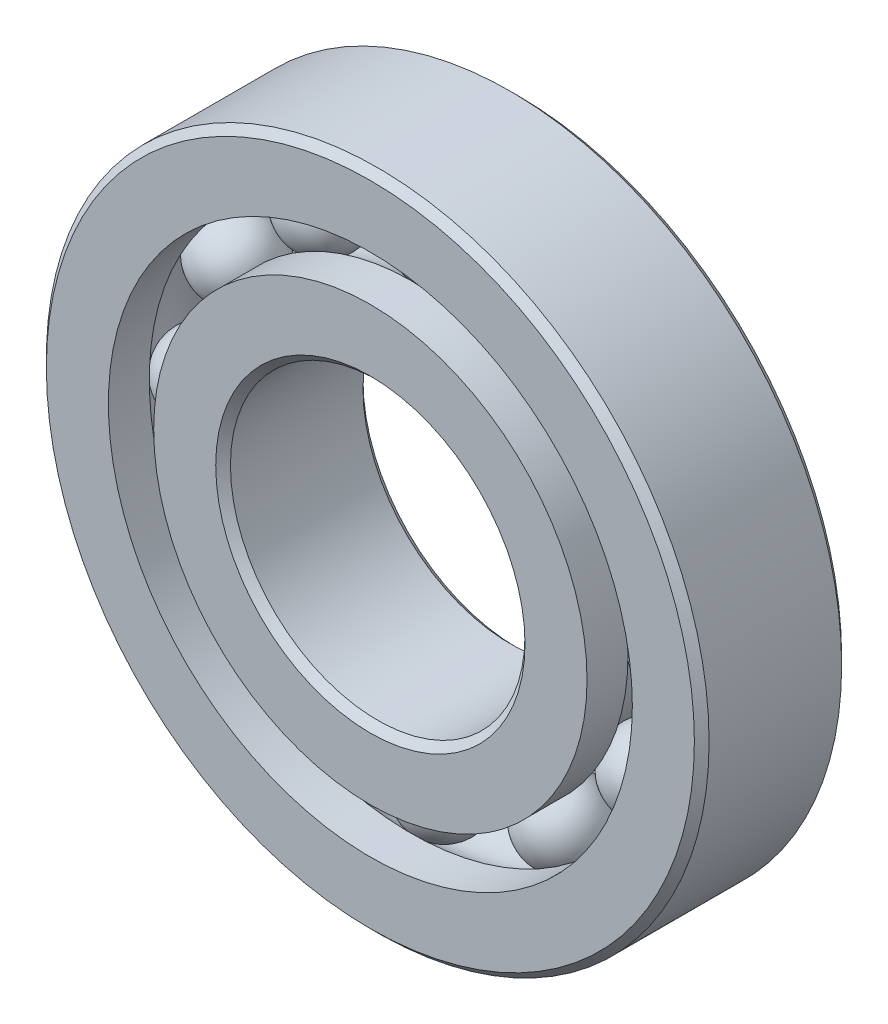
SolidWorks part; units mm, degrees
ref_plane "Front Plane" through (0, 0, 0) normal (0, 0, 1) x (1, 0, 0)
ref_plane "Top Plane" through (0, 0, 0) normal (0, 1, 0) x (1, 0, 0)
ref_plane "Right Plane" through (0, 0, 0) normal (1, 0, 0) x (0, 0, -1)
sketch "Sketch1" plane through (0, 0, 0) normal (1, 0, 0) x (0, 0, -1)
  line L0 (-3.175, 0) -> (3.175, 0) construction
  line L1 (0, 14.2875) -> (0, -14.2875) construction
  line L2 (2.8575, 14.2875) -> (-2.8575, 14.2875)
  line L3 (-2.8575, 14.2875) -> (-3.175, 13.97)
  line L4 (-3.175, 13.97) -> (-3.175, 11.2957)
  line L5 (-3.175, 11.2957) -> (-1.4111, 11.2957)
  line L6 (3.175, 11.2957) -> (1.4111, 11.2957)
  line L7 (3.175, 13.97) -> (3.175, 11.2957)
  line L8 (2.8575, 14.2875) -> (3.175, 13.97)
  line L9 (0, 14.2875) -> (0, 10.3187) construction
  line L10 (0, 10.3187) -> (0, 6.35) construction
  arc A0 (-1.4111, 11.2957) -> (1.4111, 11.2957) centre (0, 10.3187) cw
  point P14 (0, 6.35)
  dimension "D3" = 2.8222
  dimension "D1" = 45
  dimension "Width" = 6.35
  dimension "OD" = 28.575
  dimension "D2" = 0.3175
  dimension "Shaft Dia" = 12.7
  dimension "D4" = 0.9769
revolve "Revolve1" add sketch "Sketch1" angle 360 about L0
sketch "Sketch3" plane through (0, 0, 0) normal (1, 0, 0) x (0, 0, -1)
  line L0 (-3.175, 9.3418) -> (-1.4111, 9.3418)
  line L1 (0, 14.2875) -> (0, -14.2875) construction
  line L2 (-3.175, 13.97) -> (-3.175, 11.2957) construction
  line L3 (-3.175, 9.3418) -> (-3.175, 6.6675)
  line L4 (-2.8575, 14.2875) -> (-3.175, 13.97) construction
  line L5 (-3.175, 6.6675) -> (-2.8575, 6.35)
  line L6 (-2.8575, 6.35) -> (2.8575, 6.35)
  line L7 (2.8575, 14.2875) -> (2.8575, -14.2875) construction
  line L8 (2.8575, 6.35) -> (3.175, 6.6675)
  line L9 (3.175, -13.97) -> (3.175, 13.97) construction
  line L10 (3.175, 6.6675) -> (3.175, 9.3418)
  line L11 (3.175, 9.3418) -> (1.4111, 9.3418)
  line L13 (2.8575, 14.2875) -> (3.175, 13.97) construction
  arc A0 (1.4111, 11.2957) -> (-1.4111, 11.2957) centre (0, 10.3187) ccw construction
  arc A1 (1.4111, 9.3418) -> (-1.4111, 9.3418) centre (0, 10.3187) cw
revolve "Revolve3" add sketch "Sketch3" angle 360 about L0
sketch "Sketch4" plane through (0, 0, 0) normal (1, 0, 0) x (0, 0, -1)
  line L0 (-1.7163, 10.3188) -> (1.7163, 10.3188)
  arc A2 (-1.7163, 10.3188) -> (1.7163, 10.3188) centre (0, 10.3187) cw
  arc A3 (1.4111, 11.2957) -> (-1.4111, 11.2957) centre (0, 10.3187) ccw construction
revolve "Revolve4" add sketch "Sketch4" angle 360 about L0
ref_axis "Axis1" through (0, 0, -3.175) along (0, 0, 1)
pattern_circular "CirPattern1" count 12 every 30 about axis through (0, 0, -3.175) along (0, 0, 1) of bodies 104
equation "\"D2@Sketch1\" = \"Width@Sketch1\"*.05"
equation "\"D3@Sketch1\" = \"Width@Sketch1\"/2.25"
equation "\"D4@Sketch1\" = (((\"OD@Sketch1\"-\"Width@Sketch1\")/2)/3.25)/3.5"
equation "\"D2@CirPattern1\" = 360/\"Balls@CirPattern1\""
